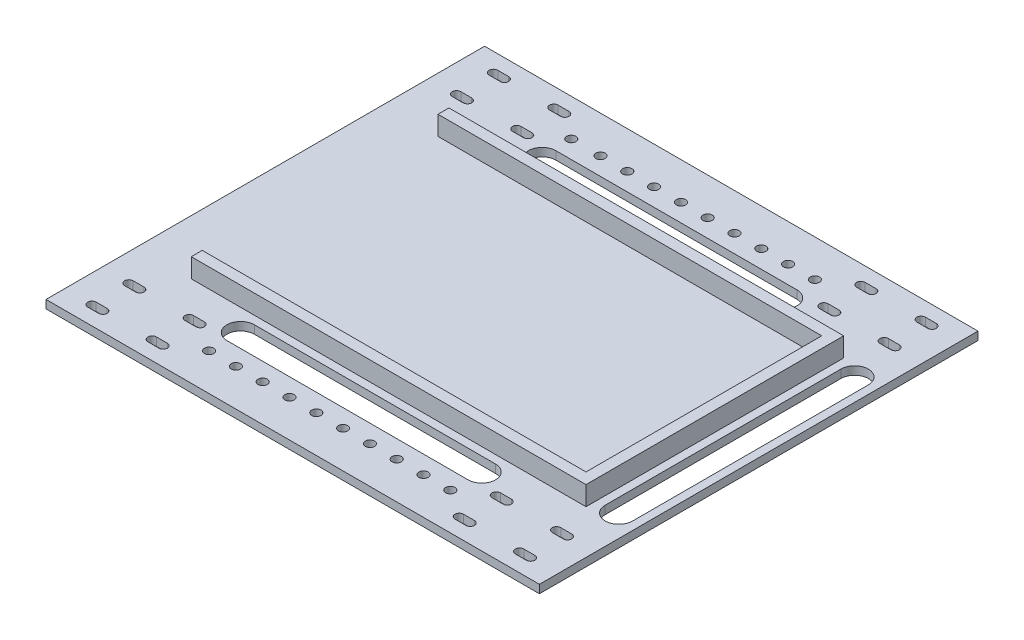
SolidWorks part; units mm, degrees
note: The reader was unsure of these and kept them because the rebuilt part matched: shared geometry of "Sketch1<3>".
ref_plane "Front Plane" through (0, 0, 0) normal (0, 0, 1) x (1, 0, 0)
ref_plane "Top Plane" through (0, 0, 0) normal (0, 1, 0) x (1, 0, 0)
ref_plane "Right Plane" through (0, 0, 0) normal (1, 0, 0) x (0, 0, -1)
sketch "Sketch1" plane through (0, 0, 0) normal (0, 1, 0) x (1, 0, 0)
  line L0 (0, -45) -> (0, 45) construction
  line L1 (-90, -80) -> (90, -80)
  line L2 (-90, -80) -> (-90, 80)
  line L3 (-90, 80) -> (90, 80)
  line L4 (90, -80) -> (90, 80)
  line L5 (-90, -80) -> (90, 80) construction
  line L6 (-90, 80) -> (90, -80) construction
  line L17 (-70, 43) -> (70, 43)
  line L18 (-70, 43) -> (-70, 47)
  line L21 (-70, 47) -> (70, 47)
  line L22 (70, 43) -> (70, 47)
  line L23 (-70, 43) -> (70, 47) construction
  line L24 (-70, 47) -> (70, 43) construction
  line L25 (-70, -47) -> (70, -47)
  line L26 (-70, -47) -> (-70, -43)
  line L27 (-70, -43) -> (70, -43)
  line L28 (70, -47) -> (70, -43)
  line L29 (-70, -47) -> (70, -43) construction
  line L30 (-70, -43) -> (70, -47) construction
  line L31 (0, 0) -> (-90, 0) construction
  line L36 (74, -47) -> (70, -47)
  line L37 (74, -47) -> (74, 47)
  line L38 (74, 47) -> (70, 47)
  line L39 (70, -47) -> (70, 47)
  line L40 (74, -47) -> (70, 47) construction
  line L41 (74, 47) -> (70, -47) construction
  line L42 (-80, -59.75) -> (-76, -59.75) construction
  line L43 (-80, -58.195) -> (-76, -58.195)
  line L44 (-80, -61.305) -> (-76, -61.305)
  line L45 (-58, -59.75) -> (-54, -59.75) construction
  line L46 (-58, -58.195) -> (-54, -58.195)
  line L47 (-58, -61.305) -> (-54, -61.305)
  line L48 (-80, -73.25) -> (-76, -73.25) construction
  line L49 (-80, -71.695) -> (-76, -71.695)
  line L50 (-80, -74.805) -> (-76, -74.805)
  line L51 (-58, -73.25) -> (-54, -73.25) construction
  line L52 (-58, -71.695) -> (-54, -71.695)
  line L53 (-58, -74.805) -> (-54, -74.805)
  line L54 (-80, 73.25) -> (-76, 73.25) construction
  line L55 (-80, 71.695) -> (-76, 71.695)
  line L56 (-80, 74.805) -> (-76, 74.805)
  line L57 (-58, 73.25) -> (-54, 73.25) construction
  line L58 (-58, 71.695) -> (-54, 71.695)
  line L59 (-58, 74.805) -> (-54, 74.805)
  line L60 (-58, 59.75) -> (-54, 59.75) construction
  line L61 (-58, 58.195) -> (-54, 58.195)
  line L62 (-58, 61.305) -> (-54, 61.305)
  line L63 (-80, 59.75) -> (-76, 59.75) construction
  line L64 (-80, 58.195) -> (-76, 58.195)
  line L65 (-80, 61.305) -> (-76, 61.305)
  line L66 (80, -73.25) -> (76, -73.25) construction
  line L67 (80, -71.695) -> (76, -71.695)
  line L68 (80, -74.805) -> (76, -74.805)
  line L69 (80, -59.75) -> (76, -59.75) construction
  line L70 (80, -58.195) -> (76, -58.195)
  line L71 (80, -61.305) -> (76, -61.305)
  line L72 (58, -59.75) -> (54, -59.75) construction
  line L73 (58, -58.195) -> (54, -58.195)
  line L74 (58, -61.305) -> (54, -61.305)
  line L75 (58, -73.25) -> (54, -73.25) construction
  line L76 (58, -71.695) -> (54, -71.695)
  line L77 (58, -74.805) -> (54, -74.805)
  line L78 (80, 59.75) -> (76, 59.75) construction
  line L79 (80, 58.195) -> (76, 58.195)
  line L80 (80, 61.305) -> (76, 61.305)
  line L81 (58, 59.75) -> (54, 59.75) construction
  line L82 (58, 58.195) -> (54, 58.195)
  line L83 (58, 61.305) -> (54, 61.305)
  line L84 (58, 73.25) -> (54, 73.25) construction
  line L85 (58, 71.695) -> (54, 71.695)
  line L86 (58, 74.805) -> (54, 74.805)
  line L87 (80, 73.25) -> (76, 73.25) construction
  line L88 (80, 71.695) -> (76, 71.695)
  line L89 (80, 74.805) -> (76, 74.805)
  line L90 (-56, 66.5) -> (56, 66.5) construction
  line L91 (-56, 73.25) -> (-56, 59.75) construction
  line L92 (56, 73.25) -> (56, 59.75) construction
  line L93 (-56, -66.5) -> (56, -66.5) construction
  line L94 (56, -73.25) -> (56, -59.75) construction
  line L95 (-56, -73.25) -> (-56, -59.75) construction
  line L96 (-44, 55) -> (44, 55) construction
  line L97 (-44, 60) -> (44, 60)
  line L98 (-44, 50) -> (44, 50)
  line L99 (-44, -55) -> (44, -55) construction
  line L100 (-44, -60) -> (44, -60)
  line L101 (-44, -50) -> (44, -50)
  line L102 (82, -43) -> (82, 43) construction
  line L103 (77, -43) -> (77, 43)
  line L104 (87, -43) -> (87, 43)
  arc A0 (-80, -58.195) -> (-80, -61.305) centre (-80, -59.75) ccw
  arc A1 (-76, -61.305) -> (-76, -58.195) centre (-76, -59.75) ccw
  arc A2 (-58, -58.195) -> (-58, -61.305) centre (-58, -59.75) ccw
  arc A3 (-54, -61.305) -> (-54, -58.195) centre (-54, -59.75) ccw
  arc A4 (-80, -71.695) -> (-80, -74.805) centre (-80, -73.25) ccw
  arc A5 (-76, -74.805) -> (-76, -71.695) centre (-76, -73.25) ccw
  arc A6 (-58, -71.695) -> (-58, -74.805) centre (-58, -73.25) ccw
  arc A7 (-54, -74.805) -> (-54, -71.695) centre (-54, -73.25) ccw
  arc A8 (-80, 71.695) -> (-80, 74.805) centre (-80, 73.25) cw
  arc A9 (-76, 74.805) -> (-76, 71.695) centre (-76, 73.25) cw
  arc A10 (-58, 71.695) -> (-58, 74.805) centre (-58, 73.25) cw
  arc A11 (-54, 74.805) -> (-54, 71.695) centre (-54, 73.25) cw
  arc A12 (-58, 58.195) -> (-58, 61.305) centre (-58, 59.75) cw
  arc A13 (-54, 61.305) -> (-54, 58.195) centre (-54, 59.75) cw
  arc A14 (-80, 58.195) -> (-80, 61.305) centre (-80, 59.75) cw
  arc A15 (-76, 61.305) -> (-76, 58.195) centre (-76, 59.75) cw
  arc A16 (80, -71.695) -> (80, -74.805) centre (80, -73.25) cw
  arc A17 (76, -74.805) -> (76, -71.695) centre (76, -73.25) cw
  arc A18 (80, -58.195) -> (80, -61.305) centre (80, -59.75) cw
  arc A19 (76, -61.305) -> (76, -58.195) centre (76, -59.75) cw
  arc A20 (58, -58.195) -> (58, -61.305) centre (58, -59.75) cw
  arc A21 (54, -61.305) -> (54, -58.195) centre (54, -59.75) cw
  arc A22 (58, -71.695) -> (58, -74.805) centre (58, -73.25) cw
  arc A23 (54, -74.805) -> (54, -71.695) centre (54, -73.25) cw
  arc A24 (80, 58.195) -> (80, 61.305) centre (80, 59.75) ccw
  arc A25 (76, 61.305) -> (76, 58.195) centre (76, 59.75) ccw
  arc A26 (58, 58.195) -> (58, 61.305) centre (58, 59.75) ccw
  arc A27 (54, 61.305) -> (54, 58.195) centre (54, 59.75) ccw
  arc A28 (58, 71.695) -> (58, 74.805) centre (58, 73.25) ccw
  arc A29 (54, 74.805) -> (54, 71.695) centre (54, 73.25) ccw
  arc A30 (80, 71.695) -> (80, 74.805) centre (80, 73.25) ccw
  arc A31 (76, 74.805) -> (76, 71.695) centre (76, 73.25) ccw
  arc A32 (-44, 60) -> (-44, 50) centre (-44, 55) ccw
  arc A33 (44, 50) -> (44, 60) centre (44, 55) ccw
  arc A34 (-44, -60) -> (-44, -50) centre (-44, -55) cw
  arc A35 (44, -50) -> (44, -60) centre (44, -55) cw
  arc A36 (77, -43) -> (87, -43) centre (82, -43) ccw
  arc A37 (87, 43) -> (77, 43) centre (82, 43) ccw
  point P0 (0, 0)
  point P6 (0, 45)
  point P7 (0, -45)
  point P19 (0, 0)
  point P21 (72, 0)
  point P27 (-78, -59.75)
  point P33 (-56, -59.75)
  point P40 (-78, -73.25)
  point P47 (-56, -73.25)
  point P56 (0, 66.5)
  point P59 (-78, 73.25)
  point P66 (-56, 73.25)
  point P73 (-56, 59.75)
  point P80 (-78, 59.75)
  point P87 (78, -73.25)
  point P94 (78, -59.75)
  point P101 (56, -59.75)
  point P108 (56, -73.25)
  point P115 (78, 59.75)
  point P122 (56, 59.75)
  point P129 (56, 73.25)
  point P136 (78, 73.25)
  point P142 (-44, 66.5)
  point P143 (-56, 66.5)
  point P144 (-34.2222, 66.5)
  point P148 (-24.4444, 66.5)
  point P149 (-14.6667, 66.5)
  point P150 (-4.8889, 66.5)
  point P151 (4.8889, 66.5)
  point P152 (14.6667, 66.5)
  point P153 (24.4444, 66.5)
  point P154 (34.2222, 66.5)
  point P155 (44, 66.5)
  point P157 (-4.8889, -66.5)
  point P158 (4.8889, -66.5)
  point P159 (14.6667, -66.5)
  point P160 (24.4444, -66.5)
  point P161 (34.2222, -66.5)
  point P162 (44, -66.5)
  point P167 (-14.6667, -66.5)
  point P168 (-24.4444, -66.5)
  point P169 (-34.2222, -66.5)
  point P170 (-44, -66.5)
  point P173 (0, 55)
  point P179 (82, 0)
  point P184 (0, -55)
  point P192 (0, 0)
  point P193 (0, 0)
  point P194 (0, 0)
  dimension "D1" = 180
  dimension "D2" = 3.11
  dimension "D3" = 86
  dimension "D4" = 4
  dimension "D5" = 140
  dimension "D6" = 4
  dimension "D7" = 18
  dimension "D8" = 13.5
  dimension "D9" = 6.75
  dimension "D10" = 10
  dimension "D11" = 160
  dimension "D12" = 12
  dimension "D14" = 10
  dimension "D15" = 8
  dimension "D16" = 10
  dimension "D17" = 8
  dimension "D13" = 10
extrude "Boss-Extrude1" add sketch "Sketch1" along normal blind 3 contours L27 L39 L17 L18 L3 L2 L1 L26 | L17 L22 L3 L18 | L39 L28 L1 L37 L3 L22 | L37 L1 L4 L3
extrude "Boss-Extrude2" add sketch "Sketch1<3>" along normal blind 10 contours L39 L28 L1 L37 L3 L22
sketch "Sketch1<3>" plane through (0, 0, 0) normal (0, 1, 0) x (1, 0, 0) same geometry as "Sketch1"
hole_wizard "M3 Clearance Hole1" positions "Sketch2" profile "Sketch3" hole size "M3" standard "ANSI Metric"
sketch "Sketch2" plane through (0, 3, 0) normal (0, 1, 0) x (1, 0, 0)
  line L0 (-56, 66.5) -> (56, 66.5) construction
  point P0 (-44, -66.5)
  point P3 (-34.2222, -66.5)
  point P6 (-24.4444, -66.5)
  point P9 (-14.6667, -66.5)
  point P12 (-4.8889, -66.5)
  point P15 (4.8889, -66.5)
  point P18 (14.6667, -66.5)
  point P21 (24.4444, -66.5)
  point P24 (34.2222, -66.5)
  point P27 (44, -66.5)
  point P30 (44, 66.5)
  point P33 (34.2222, 66.5)
  point P36 (24.4444, 66.5)
  point P39 (14.6667, 66.5)
  point P42 (4.8889, 66.5)
  point P45 (-4.8889, 66.5)
  point P48 (-14.6667, 66.5)
  point P51 (-24.4444, 66.5)
  point P54 (-34.2222, 66.5)
  point P57 (-44.8813, 66.5)
sketch "Sketch3" plane through (-44, 3, 66.5) normal (1, 0, 0) x (0, 0, 1)
  line L0 (0, 0) -> (0, 4.0205)
  line L1 (0, 4.0205) -> (1.7, 2.999)
  line L2 (1.7, 2.999) -> (1.7, 0)
  line L5 (1.7, 0) -> (0, 0)
  line L10 (0, 4.0205) -> (-1.7, 2.999) construction
  line L11 (0, -6.35) -> (0, 107.95) construction
  dimension "Hole Dia." = 3.4
  dimension "Hole Depth" = 2.999
  dimension "Drill Angle" = 118
sketch "Sketch4" plane through (0, 0, 0) normal (0, -1, 0) x (1, 0, 0)
  line L0 (90, 80) -> (90, -80) construction
  line L1 (3.5, -24.5) -> (61.5, -24.5) construction
  line L2 (3.5, -24.5) -> (3.5, 24.5) construction
  line L3 (3.5, 24.5) -> (61.5, 24.5) construction
  line L4 (61.5, -24.5) -> (61.5, 24.5) construction
  line L5 (3.5, -24.5) -> (61.5, 24.5) construction
  line L6 (3.5, 24.5) -> (61.5, -24.5) construction
  line L7 (-90, 80) -> (-90, -80) construction
  line L8 (-80, 17.255) -> (-45.84, 17.255) construction
  line L9 (-80, 17.255) -> (-80, -17.255) construction
  line L10 (-80, -17.255) -> (-45.84, -17.255) construction
  line L11 (-45.84, 17.255) -> (-45.84, -17.255) construction
  line L12 (-80, 17.255) -> (-45.84, -17.255) construction
  line L13 (-80, -17.255) -> (-45.84, 17.255) construction
  circle A0 centre (3.5, 24.5) radius 3
  circle A1 centre (61.5, 24.5) radius 3
  circle A2 centre (61.5, -24.5) radius 3
  circle A3 centre (3.5, -24.5) radius 3
  circle A4 centre (3.5, 24.5) radius 1.45
  circle A5 centre (61.5, 24.5) radius 1.45
  circle A6 centre (61.5, -24.5) radius 1.45
  circle A7 centre (3.5, -24.5) radius 1.45
  circle A8 centre (-80, 17.255) radius 1.45
  circle A9 centre (-45.84, 17.255) radius 1.45
  circle A10 centre (-45.84, -17.255) radius 1.45
  circle A11 centre (-80, -17.255) radius 1.45
  circle A12 centre (-80, 17.255) radius 3
  circle A13 centre (-45.84, 17.255) radius 3
  circle A14 centre (-45.84, -17.255) radius 3
  circle A15 centre (-80, -17.255) radius 3
  point P0 (32.5, 0)
  point P19 (-62.92, 0)
  dimension "D3" = 6
  dimension "D4" = 2.9
  dimension "D6" = 34.16
  dimension "D9" = 2.9
  dimension "D10" = 6
  dimension "D1" = 58
  dimension "D2" = 49
  dimension "D5" = 28.5
  dimension "D7" = 34.51
  dimension "D8" = 10
extrude "Boss-Extrude3" add sketch "Sketch4" along normal blind 5
fillet "Fillet2" radius 2.5 8 edges at (61.5, 0, 27.5) (61.5, 0, -21.5) (3.5, 0, -21.5) (3.5, 0, 27.5) (-80, 0, -14.255) (-45.84, 0, -14.255) (-45.84, 0, 20.255) (-80, 0, 20.255) curvature continuous yes
